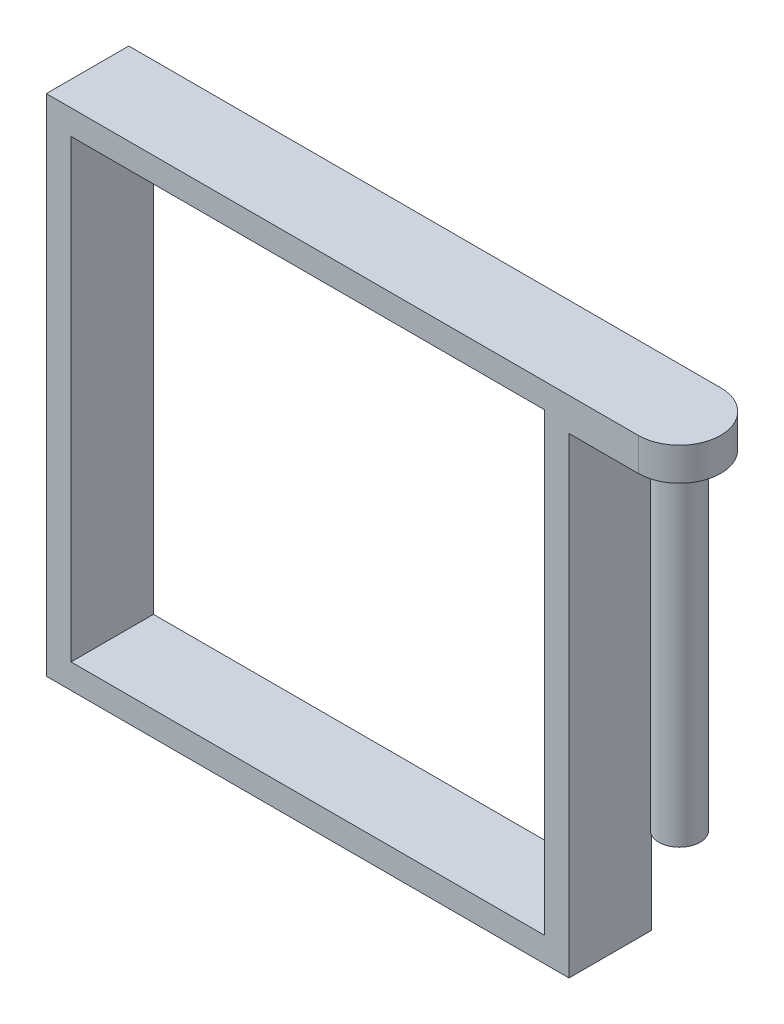
SolidWorks part; units mm, degrees
ref_plane "Front Plane" through (0, 0, 0) normal (0, 0, 1) x (1, 0, 0)
ref_plane "Top Plane" through (0, 0, 0) normal (0, 1, 0) x (1, 0, 0)
ref_plane "Right Plane" through (0, 0, 0) normal (1, 0, 0) x (0, 0, -1)
sketch "Sketch1" plane through (0, 0, 0) normal (0, 0, 1) x (1, 0, 0)
  line L1 (0, 0) -> (72.898, 0)
  line L2 (0, 0) -> (0, 70.104)
  line L3 (0, 70.104) -> (72.898, 70.104)
  line L4 (72.898, 0) -> (72.898, 70.104)
  line L5 (-3.81, 73.914) -> (76.708, 73.914)
  line L6 (-3.81, 73.914) -> (-3.81, -3.81)
  line L7 (-3.81, -3.81) -> (76.708, -3.81)
  line L8 (76.708, 73.914) -> (76.708, -3.81)
  dimension "D1" = 3.81
  dimension "D2" = 3.81
  dimension "D3" = 3.81
  dimension "D4" = 3.81
  dimension "D5" = 72.898
  dimension "D6" = 70.104
extrude "Boss-Extrude1" add sketch "Sketch1" along normal blind 12.7
sketch "Sketch5" plane through (0, 73.914, 0) normal (0, 1, 0) x (1, 0, 0)
  line L0 (76.708, -12.7) -> (76.708, 0) construction
  line L1 (87.376, 0) -> (76.708, 0)
  line L2 (76.708, 0) -> (76.708, -12.7)
  line L3 (76.708, -12.7) -> (87.376, -12.7)
  line L4 (72.898, -12.7) -> (72.898, 0) construction
  arc A0 (87.376, -12.7) -> (87.376, 0) centre (87.376, -6.35) ccw
  point P2 (76.708, -6.35)
  dimension "D1" = 12.7
  dimension "D2" = 14.478
extrude "Boss-Extrude4" add sketch "Sketch5" against normal blind 5.08 contours A0 L1 L2 L3
sketch "Sketch6" plane through (0, 68.834, 0) normal (0, -1, 0) x (1, 0, 0)
  circle A0 centre (87.376, 6.35) radius 3.175
  arc A1 (87.376, 0) -> (87.376, 12.7) centre (87.376, 6.35) ccw construction
  dimension "D1" = 6.35
extrude "Boss-Extrude5" add sketch "Sketch6" along normal blind 50.8
sketch "Sketch7" plane through (0, 68.834, 0) normal (0, -1, 0) x (1, 0, 0)
  line L1 (83.5316, 6.35) -> (85.9832, 6.35)
  line L2 (83.5316, 6.35) -> (83.5316, 4.9416)
  line L3 (83.5316, 4.9416) -> (85.9832, 4.9416)
  line L4 (85.9832, 6.35) -> (85.9832, 4.9416)
  arc A0 (87.376, 0) -> (87.376, 12.7) centre (87.376, 6.35) ccw construction
  point P4 (93.726, 6.35)
extrude "Boss-Extrude6" add sketch "Sketch7" along normal blind 2.54
